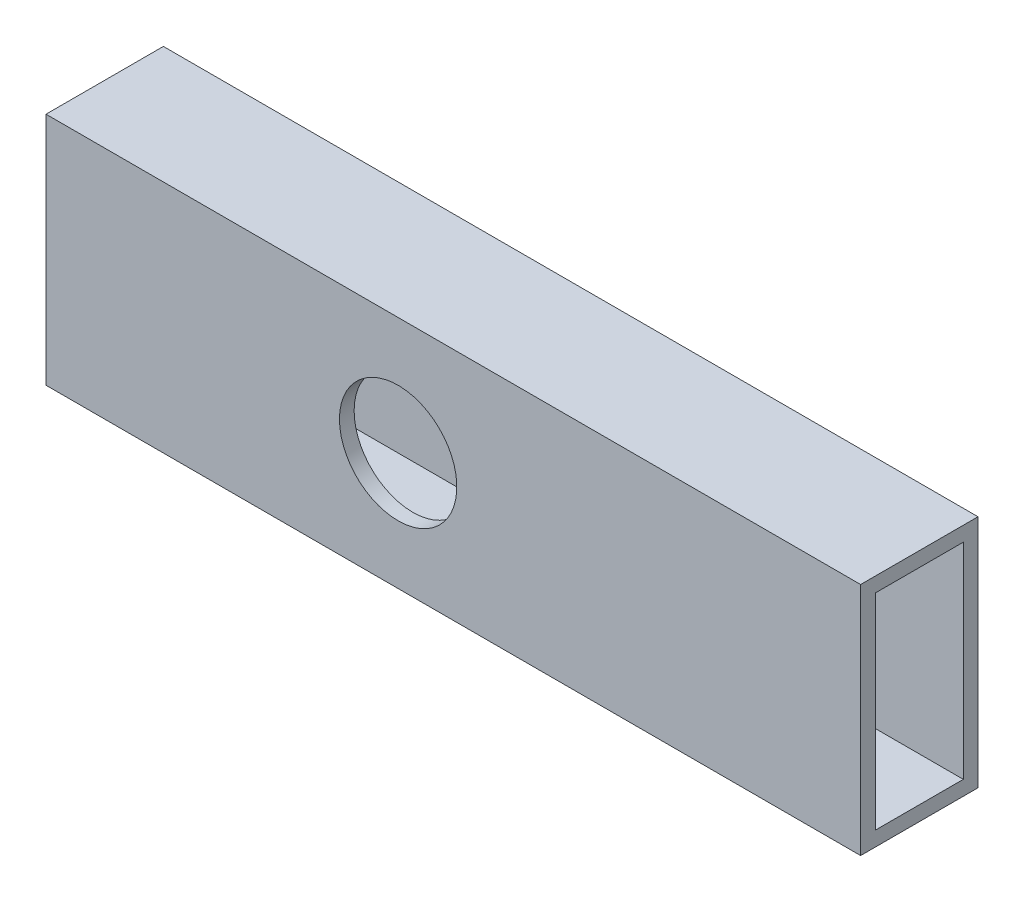
SolidWorks part; units mm, degrees
ref_plane "Front Plane" through (0, 0, 0) normal (0, 0, 1) x (1, 0, 0)
ref_plane "Top Plane" through (0, 0, 0) normal (0, 1, 0) x (1, 0, 0)
ref_plane "Right Plane" through (0, 0, 0) normal (1, 0, 0) x (0, 0, -1)
sketch "Sketch1" plane through (0, 0, 0) normal (0, 1, 0) x (1, 0, 0)
  line L1 (0, 0) -> (176.276, 0)
  line L2 (0, 0) -> (0, 25.4)
  line L3 (0, 25.4) -> (176.276, 25.4)
  line L4 (176.276, 0) -> (176.276, 25.4)
  dimension "D1" = 176.276
  dimension "D2" = 25.4
extrude "Boss-Extrude1" add sketch "Sketch1" along normal blind 50.8
sketch "Sketch2" plane through (176.276, 0, 0) normal (1, 0, 0) x (0, 0, -1)
  line L0 (3.175, 47.625) -> (3.175, 3.175)
  line L1 (0, 50.8) -> (25.4, 50.8)
  line L2 (0, 50.8) -> (0, 0)
  line L3 (0, 0) -> (25.4, 0)
  line L4 (25.4, 50.8) -> (25.4, 0)
  line L5 (3.175, 3.175) -> (22.225, 3.175)
  line L6 (22.225, 47.625) -> (22.225, 3.175)
  line L7 (3.175, 47.625) -> (22.225, 47.625)
  dimension "D1" = 3.175
extrude "Cut-Extrude1" cut sketch "Sketch2" against normal through all flip side to cut
sketch "Sketch3" plane through (0, 0, -25.4) normal (0, 0, -1) x (-1, 0, 0)
  line L1 (-176.276, 50.8) -> (0, 50.8) construction
  line L2 (0, 50.8) -> (0, 0) construction
  circle A0 centre (-76.2, 25.4) radius 12.7
  dimension "D1" = 25.4
  dimension "D4" = 76.2
  dimension "D3" = 25.4
extrude "Cut-Extrude2" cut sketch "Sketch3" against normal through all
